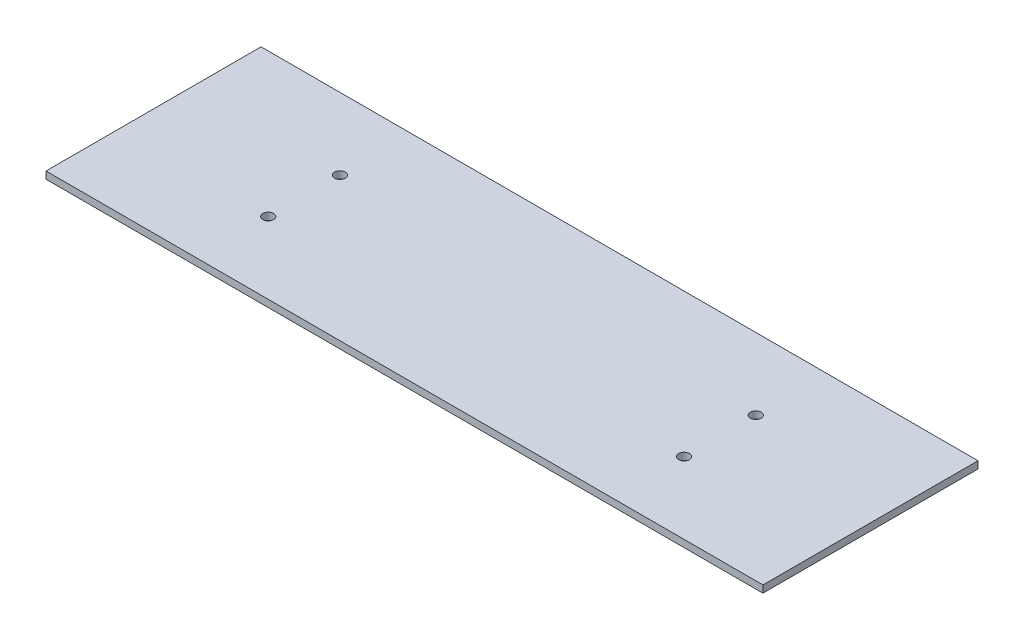
SolidWorks part; units mm, degrees
ref_plane "Front Plane" through (0, 0, 0) normal (0, 0, 1) x (1, 0, 0)
ref_plane "Top Plane" through (0, 0, 0) normal (0, 1, 0) x (1, 0, 0)
ref_plane "Right Plane" through (0, 0, 0) normal (1, 0, 0) x (0, 0, -1)
sketch "Sketch1" plane through (0, 0, 0) normal (0, 1, 0) x (1, 0, 0)
  line L1 (0, 0) -> (200, 0)
  line L2 (0, 0) -> (0, 60)
  line L3 (0, 60) -> (200, 60)
  line L4 (200, 0) -> (200, 60)
  line L5 (42, 40) -> (158, 40)
  line L6 (42, 40) -> (42, 20)
  line L7 (42, 20) -> (158, 20)
  line L8 (158, 40) -> (158, 20)
  circle A0 centre (42, 40) radius 1.5
  circle A1 centre (42, 20) radius 1.5
  circle A3 centre (158, 40) radius 1.5
  circle A4 centre (158, 20) radius 1.5
  point P11 (0, 0)
  point P12 (0, 0)
  point P13 (0, 0)
  point P14 (0, 0)
  point P17 (157.5751, 40)
  point P19 (158, 19.468)
  dimension "D1" = 60
  dimension "D2" = 200
  dimension "D3" = 20
  dimension "D4" = 116
  dimension "D5" = 20
  dimension "D6" = 42
  dimension "D7" = 42
extrude "Boss-Extrude1" add sketch "Sketch1" along normal blind 2 contours L1 L4 L3 L2 A4 L7 A1 L6 A0 L5 A3 L8 | A4 L8 A3 L5 A0 L6 A1 L7 region at (2.0881, 0, -30) region at (100, 0, -30)
